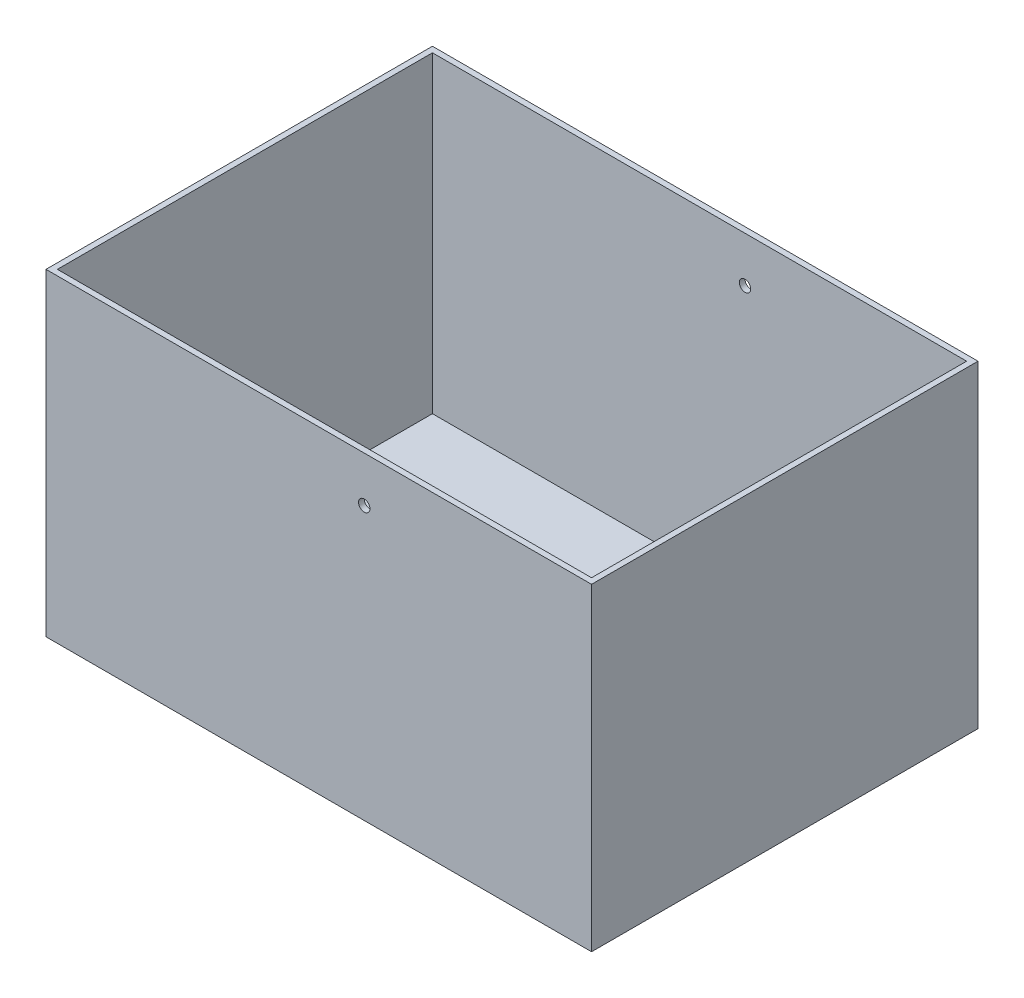
SolidWorks part; units mm, degrees
ref_plane "Front Plane" through (0, 0, 0) normal (0, 0, 1) x (1, 0, 0)
ref_plane "Top Plane" through (0, 0, 0) normal (0, 1, 0) x (1, 0, 0)
ref_plane "Right Plane" through (0, 0, 0) normal (1, 0, 0) x (0, 0, -1)
sketch "Sketch1" plane through (0, 0, 0) normal (0, 1, 0) x (1, 0, 0)
  line L0 (-149.225, 107.95) -> (-149.225, 104.775) construction
  line L1 (-152.4, 107.95) -> (152.4, 107.95)
  line L2 (-152.4, 107.95) -> (-152.4, -107.95)
  line L3 (-152.4, -107.95) -> (152.4, -107.95)
  line L4 (152.4, 107.95) -> (152.4, -107.95)
  line L5 (-152.4, 107.95) -> (152.4, -107.95) construction
  line L6 (-152.4, -107.95) -> (152.4, 107.95) construction
  line L7 (-149.225, -104.775) -> (149.225, -104.775)
  line L8 (-149.225, -104.775) -> (-149.225, 104.775)
  line L9 (-149.225, 104.775) -> (149.225, 104.775)
  line L10 (149.225, -104.775) -> (149.225, 104.775)
  line L11 (-149.225, -104.775) -> (149.225, 104.775) construction
  line L12 (-149.225, 104.775) -> (149.225, -104.775) construction
  line L13 (-149.225, 104.775) -> (-152.4, 104.775) construction
  point P0 (0, 0)
  point P6 (0, 0)
  dimension "D1" = 304.8
  dimension "D2" = 215.9
  dimension "D3" = 3.175
extrude "Boss-Extrude1" add sketch "Sketch1" along normal blind 3.175 contours L7 L10 L9 L8 region at (0, 0, 0)
extrude "Boss-Extrude2" add sketch "Sketch1<3>" along normal blind 177.8
sketch "Sketch1<3>" plane through (0, 0, 0) normal (0, 1, 0) x (1, 0, 0) same geometry as "Sketch1"
sketch "Sketch2" plane through (0, 0, 107.95) normal (0, 0, 1) x (1, 0, 0)
  line L0 (25.4, 152.4) -> (152.4, 152.4) construction
  line L1 (152.4, 177.8) -> (152.4, 0) construction
  line L2 (25.4, 152.4) -> (25.4, 177.8) construction
  line L3 (-152.4, 177.8) -> (152.4, 177.8) construction
  circle A0 centre (25.4, 152.4) radius 3.175
  dimension "D1" = 6.35
  dimension "D2" = 25.4
  dimension "D3" = 127
extrude "Cut-Extrude1" cut sketch "Sketch2" against normal through all both and the other way through all
